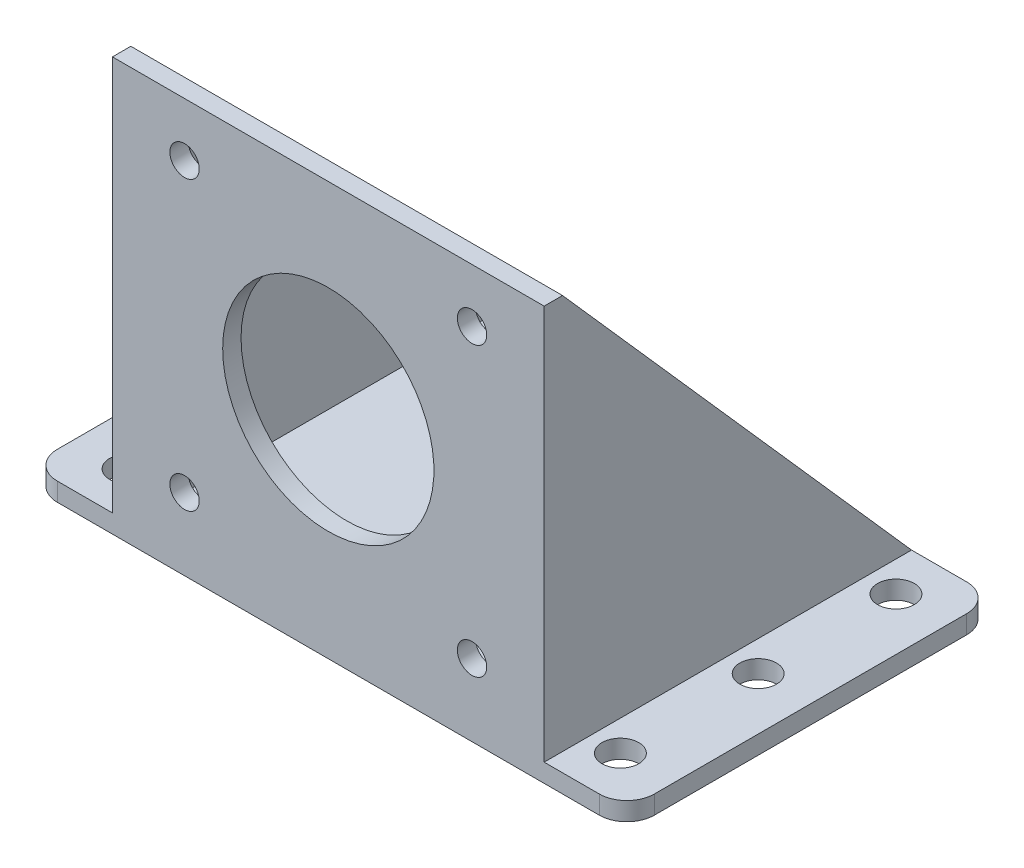
SolidWorks part; units mm, degrees
ref_plane "前视基准面" through (0, 0, 0) normal (0, 0, 1) x (1, 0, 0)
ref_plane "上视基准面" through (0, 0, 0) normal (0, 1, 0) x (1, 0, 0)
ref_plane "右视基准面" through (0, 0, 0) normal (1, 0, 0) x (0, 0, -1)
sketch "草图1" plane through (0, 0, 0) normal (0, 1, 0) x (1, 0, 0)
  line L1 (0, 0) -> (65, 0)
  line L2 (0, 0) -> (0, 40)
  line L3 (0, 40) -> (65, 40)
  line L4 (65, 0) -> (65, 40)
  dimension "D1" = 40
  dimension "D2" = 65
extrude "凸台-拉伸1" add sketch "草图1" along normal blind 2
ref_plane "基准面1" through (32.5, 0, 0) normal (-1, 0, 0) x (0, 0, 1)
ref_plane "基准面2" through (0, 0, -20) normal (0, 0, 1) x (1, 0, 0)
sketch "草图2" plane through (0, 2, 0) normal (0, 1, 0) x (1, 0, 0)
  line L0 (32.5, 1.1) -> (32.5, -1.1) construction
  line L1 (-1.1, 20) -> (1.1, 20) construction
  circle A0 centre (5.7, 5) radius 2
  circle A1 centre (5.7, 20) radius 2
  circle A2 centre (5.7, 35) radius 2
  circle A4 centre (59.3, 5) radius 2
  circle A5 centre (59.3, 20) radius 2
  circle A6 centre (59.3, 35) radius 2
  dimension "D6" = 4
  dimension "D7" = 4
  dimension "D8" = 4
  dimension "D1" = 26.8
  dimension "D2" = 26.8
  dimension "D3" = 26.8
  dimension "D4" = 15
  dimension "D5" = 15
  dimension "D9" = 15
extrude "切除-拉伸1" cut sketch "草图2" against normal through all
sketch "草图3" plane through (0, 0, 0) normal (0, 0, 1) x (1, 0, 0)
  line L0 (9, 2) -> (56, 2)
  line L1 (0, 2) -> (65, 2) construction
  line L2 (9, 2) -> (9, 45)
  line L3 (9, 45) -> (56, 45)
  line L6 (56, 2) -> (56, 45)
  line L7 (32.5, 1.1) -> (32.5, -1.1) construction
  point P7 (41.8848, 8.6708)
  dimension "D1" = 43
  dimension "D2" = 47
  dimension "D3" = 23.5
extrude "凸台-拉伸2" add sketch "草图3" against normal blind 2
sketch "草图5" plane through (9, 0, 0) normal (-1, 0, 0) x (0, 0, 1)
  line L0 (-40, 2) -> (-2, 45)
rib "筋1" sketch "草图5" sketch "草图5" thickness 2 extrusion direction parallel to sketch draft on no parameters "D1"=2
sketch "草图6" plane through (56, 0, 0) normal (1, 0, 0) x (0, 0, -1)
  line L0 (2, 45) -> (40, 2)
rib "筋2" sketch "草图6" sketch "草图6" thickness 2 extrusion direction parallel to sketch draft on no parameters "D1"=2
sketch "草图7" plane through (0, 0, -2) normal (0, 0, -1) x (-1, 0, 0)
  line L0 (-9, 2) -> (-9, 45) construction
  line L1 (-54, 45) -> (-11, 45) construction
  circle A0 centre (-32.5, 23.5) radius 11.5
  circle A1 centre (-48.15, 7.85) radius 1.6
  circle A2 centre (-16.85, 7.85) radius 1.6
  circle A3 centre (-16.85, 39.15) radius 1.6
  circle A4 centre (-48.15, 39.15) radius 1.6
  dimension "D1" = 23
  dimension "D3" = 3.2
  dimension "D2" = 23.5
  dimension "D4" = 15.65
  dimension "D5" = 15.65
  dimension "D6" = 21.5
  dimension "D7" = 2
  dimension "D8" = 2
extrude "切除-拉伸2" cut sketch "草图7" against normal through all
fillet "圆角1" radius 3 4 edges at (65, 1, -40) (65, 1, 0) (0, 1, -40) (0, 1, 0)
